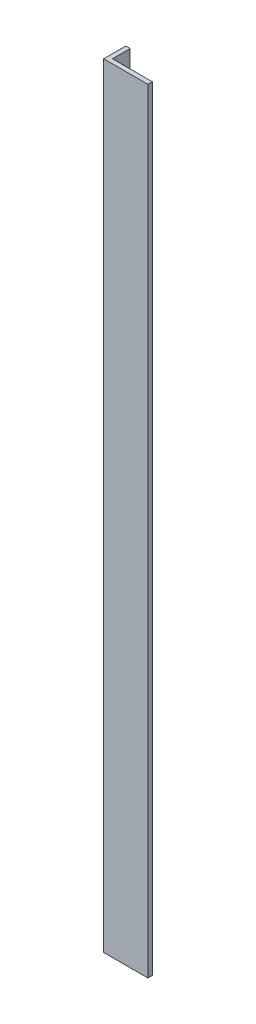
SolidWorks part; units mm, degrees
ref_plane "Front Plane" through (0, 0, 0) normal (0, 0, 1) x (1, 0, 0)
ref_plane "Top Plane" through (0, 0, 0) normal (0, 1, 0) x (1, 0, 0)
ref_plane "Right Plane" through (0, 0, 0) normal (1, 0, 0) x (0, 0, -1)
sketch "Sketch1" plane through (0, 0, 0) normal (0, 1, 0) x (1, 0, 0)
  line L0 (0, 0) -> (0, 10)
  line L1 (0, 10) -> (2, 10)
  line L2 (2, 10) -> (2, 2)
  line L3 (2, 2) -> (20, 2)
  line L4 (20, 2) -> (20, 0)
  line L5 (20, 0) -> (0, 0)
extrude "Boss-Extrude1" add sketch "Sketch1" along normal blind 350
hole_wizard "Ø3.0 (3) Diameter Hole1" positions "Sketch2" profile "Sketch3" hole size "Ø3.0" standard "ISO" end condition through all
sketch "Sketch2" plane through (2, -11.4076, -188.68) normal (1, 0, 0) x (0, 0, -1)
  point P0 (-182.68, 17.4076)
  point P1 (-182.68, 31.4076)
sketch "Sketch3" plane through (2, 6, -6) normal (0, 1, 0) x (0, 0, -1)
  line L0 (0, 0) -> (0, 2)
  line L1 (0, 2) -> (1.5, 2)
  line L2 (1.5, 2) -> (1.5, 0)
  line L3 (1.5, 0) -> (0, 0)
  line L4 (0, -6.35) -> (0, 107.95) construction
  dimension "Thru Hole Dia." = 3
  dimension "Thru Hole Depth" = 2
hole_wizard "Ø3.0 (3) Diameter Hole2" positions "Sketch4" profile "Sketch5" hole size "Ø3.0" standard "ISO" end condition through all
sketch "Sketch4" plane through (2, -11.4076, -188.68) normal (1, 0, 0) x (0, 0, -1)
  point P0 (-182.68, 355.4076)
  point P1 (-182.68, 341.4076)
sketch "Sketch5" plane through (2, 344, -6) normal (0, 1, 0) x (0, 0, -1)
  line L0 (0, 0) -> (0, 2)
  line L1 (0, 2) -> (1.5, 2)
  line L2 (1.5, 2) -> (1.5, 0)
  line L3 (1.5, 0) -> (0, 0)
  line L4 (0, -6.35) -> (0, 107.95) construction
  dimension "Thru Hole Dia." = 3
  dimension "Thru Hole Depth" = 2
